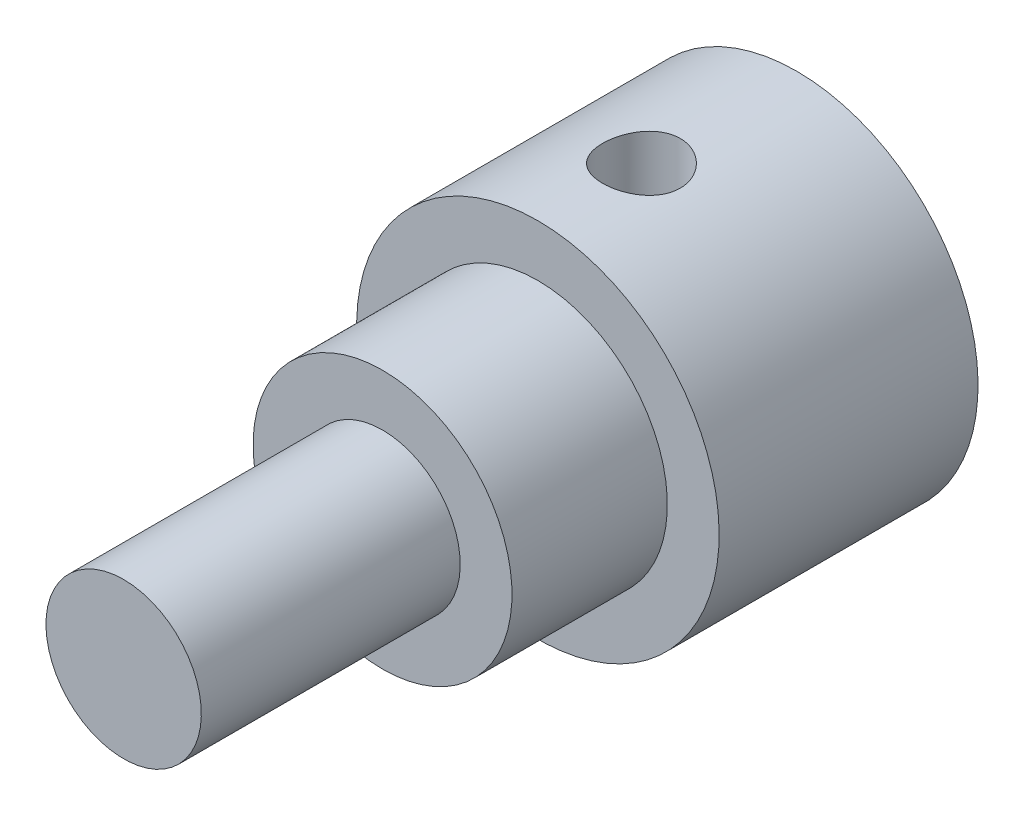
SolidWorks part; units mm, degrees
material "1060 Alloy"
ref_plane "Front Plane" through (0, 0, 0) normal (0, 0, 1) x (1, 0, 0)
ref_plane "Top Plane" through (0, 0, 0) normal (0, 1, 0) x (1, 0, 0)
ref_plane "Right Plane" through (0, 0, 0) normal (1, 0, 0) x (0, 0, -1)
sketch "Sketch1" plane through (0, 0, 0) normal (1, 0, 0) x (0, 0, -1)
  line L0 (0, 0) -> (0, 3)
  line L1 (0, 3) -> (10, 3)
  line L2 (10, 3) -> (10, 5)
  line L3 (10, 5) -> (16, 5)
  line L4 (16, 5) -> (16, 7)
  line L5 (16, 7) -> (26, 7)
  line L6 (16.5772, 0) -> (18.5, 3.2)
  line L7 (16.5772, 0) -> (0, 0)
  line L8 (18.5, 3.2) -> (26, 3.2)
  line L9 (26, 3.2) -> (26, 7)
  dimension "D1" = 3
  dimension "D2" = 10
  dimension "D3" = 6
  dimension "D4" = 5
  dimension "D5" = 10
  dimension "D6" = 7
  dimension "D7" = 3.2
  dimension "D8" = 2.5
  dimension "D9" = 121
revolve "Revolve1" add sketch "Sketch1" angle 360 about L7
sketch "Sketch2" plane through (0, 0, 0) normal (0, 1, 0) x (1, 0, 0)
  line L1 (-7, 16) -> (7, 16) construction
  circle A0 centre (0, 20) radius 1.5
  dimension "D2" = 3
  dimension "D1" = 4
extrude "Cut-Extrude1" cut sketch "Sketch2" against normal up to next and the other way up to next
